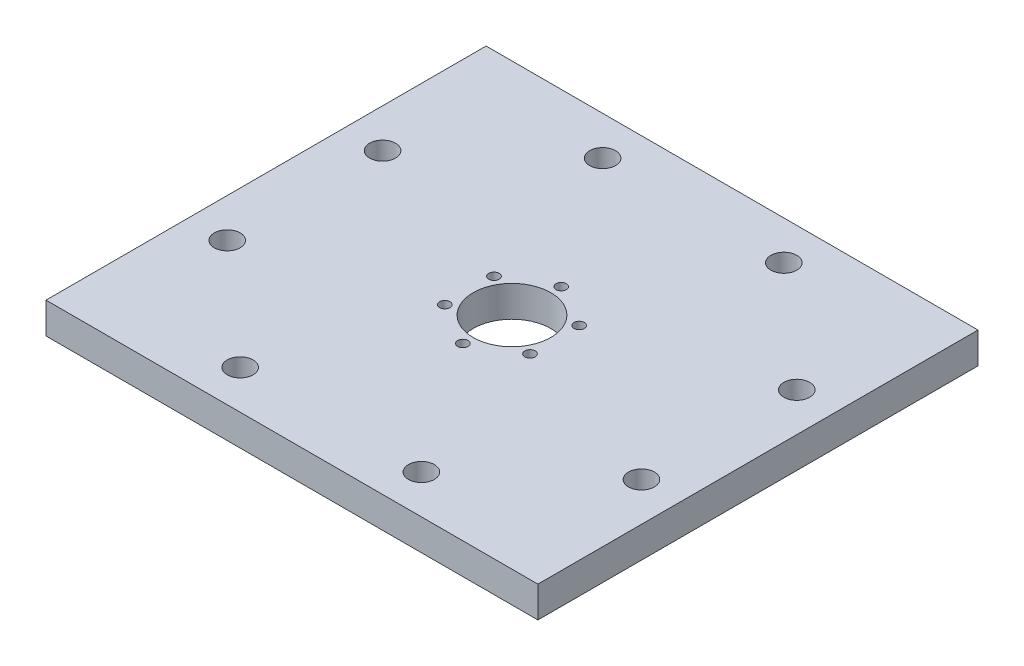
SolidWorks part; units mm, degrees
ref_plane "Front Plane" through (0, 0, 0) normal (0, 0, 1) x (1, 0, 0)
ref_plane "Top Plane" through (0, 0, 0) normal (0, 1, 0) x (1, 0, 0)
ref_plane "Right Plane" through (0, 0, 0) normal (1, 0, 0) x (0, 0, -1)
sketch "Sketch1" plane through (0, 0, 0) normal (0, 1, 0) x (1, 0, 0)
  line L0 (0, -55) -> (0, 55) construction
  line L1 (-47.5, 42.5) -> (47.5, 42.5)
  line L2 (-47.5, 42.5) -> (-47.5, -42.5)
  line L3 (-47.5, -42.5) -> (47.5, -42.5)
  line L4 (47.5, 42.5) -> (47.5, -42.5)
  line L5 (-47.5, 42.5) -> (47.5, -42.5) construction
  line L6 (-47.5, -42.5) -> (47.5, 42.5) construction
  line L7 (-55, 0) -> (55, 0) construction
  circle A0 centre (0, 0) radius 9.5 construction
  circle A1 centre (0, 9.5) radius 1
  circle A2 centre (8.2272, 4.75) radius 1
  circle A3 centre (8.2272, -4.75) radius 1
  circle A4 centre (0, -9.5) radius 1
  circle A5 centre (-8.2272, -4.75) radius 1
  circle A6 centre (-8.2272, 4.75) radius 1
  circle A7 centre (0, 0) radius 7.5
  circle A8 centre (-17.5, 35) radius 2.5
  circle A9 centre (17.5, 35) radius 2.5
  circle A10 centre (17.5, -35) radius 2.5
  circle A11 centre (-17.5, -35) radius 2.5
  circle A12 centre (-40, 15) radius 2.5
  circle A13 centre (-40, -15) radius 2.5
  circle A14 centre (40, -15) radius 2.5
  circle A15 centre (40, 15) radius 2.5
  point P34 (0, 0)
  point P37 (-1.4426, 0.0933)
  point P38 (-0.369, 0.3302)
  point P39 (-124.9144, 62.7775)
  point P40 (-120.9218, 64.1749)
  dimension "D1" = 19
  dimension "D2" = 2
  dimension "D4" = 15
  dimension "D7" = 5
  dimension "D10" = 5
  dimension "D5" = 17.5
  dimension "D6" = 95
  dimension "D8" = 85
  dimension "D9" = 35
  dimension "D11" = 40
  dimension "D12" = 15
  dimension "D3" = 6
extrude "Boss-Extrude1" add sketch "Sketch1" along normal blind 6
sketch "Sketch2" plane through (0, 0, 0) normal (0, 1, 0) x (1, 0, 0)
  line L0 (-55, 0) -> (55, 0) construction
  line L1 (0, -55) -> (0, 55) construction
  circle A0 centre (-17.5, 35) radius 6
  circle A1 centre (-17.5, -35) radius 6
  circle A2 centre (17.5, -35) radius 6
  circle A3 centre (17.5, 35) radius 6
  dimension "D1" = 12
extrude "Cut-Extrude2" cut sketch "Sketch2" along normal blind 1.5
equation "\"testbed_height\" = 91.50mm"
equation "\"plate_thickness\" = 6mm"
equation "\"main_body_splay_length\" = 48.5mm"
equation "\"splay_shaft_length_no_wires\" = 10mm"
equation "\"splay_shaft_length_wires\" = 6.5mm"
equation "\"timing_pulley_offset\" = 0mm"
equation "\"effective_motor_length\" = \"timing_pulley_offset\" + \"splay_shaft_length_no_wires\" + \"main_body_splay_length\""
equation "\"80_20_side\" = 25.4mm"
equation "\"80_20_length\" = 152.4mm"
equation "\"80_20_optic_mount_length\" = \"80_20_length\" - 25.4mm"
equation "\"optic_board_hole_size\" = 6.35mm"
equation "\"total_mounting_length\" = \"testbed_height\" - \"effective_motor_length\" - \"80_20_side\""
equation "\"mounting_vertical_portion_height\" = \"total_mounting_length\" - 2 * \"plate_thickness\""
equation "\"face_mount_width\" = 15.25mm"
equation "\"center_dist_to_face_mount_vertical_screws\" = 5mm"
equation "\"D1@Boss-Extrude1\"=\"plate_thickness\""
